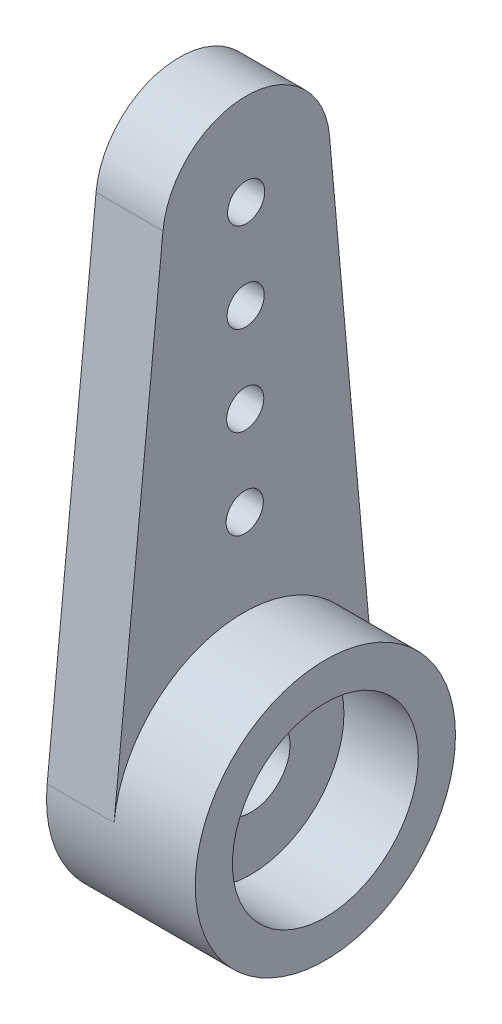
SolidWorks part; units mm, degrees
ref_plane "Ön Düzlem" through (0, 0, 0) normal (0, 0, 1) x (1, 0, 0)
ref_plane "Üst Düzlem" through (0, 0, 0) normal (0, 1, 0) x (1, 0, 0)
ref_plane "Sağ Düzlem" through (0, 0, 0) normal (1, 0, 0) x (0, 0, -1)
sketch "Çizim1" plane through (0, 0, 0) normal (1, 0, 0) x (0, 0, -1)
  line L0 (755.3131, 431.3052) -> (755.3131, 1152.7774) construction
  line L1 (585.5923, 411.3307) -> (585.5923, 430.4307) construction
  line L2 (585.5348, 415.0559) -> (585.618, 430.5559) construction
  line L3 (582.0523, 415.4048) -> (583.3671, 428.5302)
  line L4 (589.0209, 415.3674) -> (587.847, 428.5062)
  circle A0 centre (585.5348, 415.0559) radius 3.5
  arc A2 (583.3671, 428.5302) -> (587.847, 428.5062) centre (585.6059, 428.3059) cw
  circle A3 centre (585.6047, 428.081) radius 0.5
  circle A4 centre (585.5918, 425.681) radius 0.5
  circle A5 centre (585.5789, 423.281) radius 0.5
  circle A6 centre (585.5661, 420.881) radius 0.5
  circle A7 centre (585.5348, 415.0559) radius 1.05
  point P21 (0, 0)
  point P22 (585.5631, 415.1069)
  point P23 (585.6047, 428.081)
  point P24 (585.5661, 415.0559)
  point P25 (0, 0)
  dimension "D2" = 7
  dimension "D3" = 15.5
  dimension "D4" = 2.25
  dimension "D5" = 1
  dimension "D6" = 2.4
  dimension "D7" = 2.4
  dimension "D9" = 2.1
  dimension "D1" = 19.1
  dimension "D8" = 2.4
extrude "Yükseklik-Ekstrüzyon1" add sketch "Çizim1" along normal blind 4 contours A0 A7 region at (0, 418.4569, -585.5531)
extrude "Yükseklik-Ekstrüzyon2" add sketch "Çizim1<5>" along normal blind 1.8 contours A2 L3 A0 L4 A6 A5 A4 A3 region at (0, 421.9508, -582.876)
sketch "Çizim1<5>" plane through (0, 0, 0) normal (1, 0, 0) x (0, 0, -1) same geometry as "Çizim1"
sketch "Çizim2" plane through (4, 0, 0) normal (1, 0, 0) x (0, 0, -1)
  circle A0 centre (585.5348, 415.0559) radius 2.5
  dimension "D1" = 5
extrude "Kes-Ekstrüzyon1" cut sketch "Çizim2" against normal blind 2
